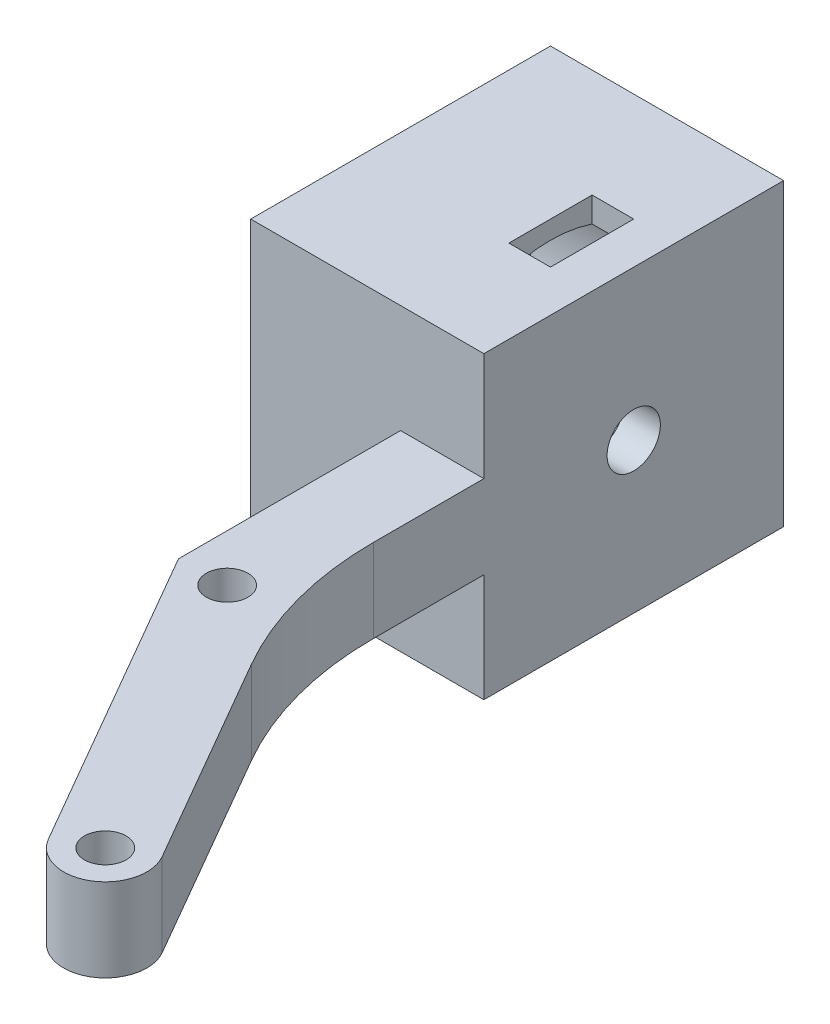
SolidWorks part; units mm, degrees
material "PLA"
ref_plane "Front Plane" through (0, 0, 0) normal (0, 0, 1) x (1, 0, 0)
ref_plane "Top Plane" through (0, 0, 0) normal (0, 1, 0) x (1, 0, 0)
ref_plane "Right Plane" through (0, 0, 0) normal (1, 0, 0) x (0, 0, -1)
sketch "Sketch1" plane through (0, 0, 0) normal (0, 1, 0) x (1, 0, 0)
  line L0 (-6.35, -14.4015) -> (-6.35, 2.54)
  line L1 (0, -12.7) -> (0, 25.4)
  line L2 (0, 25.4) -> (-17.78, 25.4)
  line L3 (-17.78, 25.4) -> (-17.78, 2.54)
  line L4 (-17.78, 2.54) -> (-6.35, 2.54)
  line L5 (0, -12.7) -> (12.7, -34.697)
  line L6 (-6.35, -14.4015) -> (7.2007, -37.872)
  line L7 (0, -12.7) -> (-5.4993, -15.875) construction
  arc A0 (7.2007, -37.872) -> (12.7, -34.697) centre (9.9504, -36.2845) ccw
  circle A1 centre (9.9504, -36.2845) radius 1.5875
  circle A2 centre (-2.7496, -14.2875) radius 1.5875
  dimension "D1" = 3.175
  dimension "D2" = 3.175
  dimension "D6" = 3.175
  dimension "D3" = 150
  dimension "D4" = 6.35
  dimension "D8" = 25.4
  dimension "D10" = 17.78
  dimension "D11" = 38.1
  dimension "D12" = 22.86
  dimension "D13" = 12.7
extrude "Boss-Extrude1" add sketch "Sketch1" along normal blind 22.86
sketch "Sketch2" plane through (0, 22.86, 0) normal (0, 1, 0) x (1, 0, 0)
  line L1 (-6.35, -14.4015) -> (8.7882, -40.6217)
  line L2 (0, -12.7) -> (14.2875, -37.4467)
  line L3 (14.2875, -37.4467) -> (8.7882, -40.6217)
  line L4 (-6.35, -14.4015) -> (7.2007, -37.872) construction
  line L5 (12.7, -34.697) -> (0, -12.7) construction
  line L6 (-6.35, 2.54) -> (0, 2.54)
  line L7 (0, -12.7) -> (0, 25.4) construction
  line L8 (0, 2.54) -> (0, -12.7)
  line L9 (-6.35, -14.4015) -> (-6.35, 2.54)
  arc A0 (7.2007, -37.872) -> (12.7, -34.697) centre (9.9504, -36.2845) ccw construction
extrude "Top Cut" cut sketch "Sketch2" against normal blind 8.255
sketch "Sketch4" plane through (0, 0, 0) normal (0, -1, 0) x (1, 0, 0)
  line L0 (-6.35, -2.54) -> (-6.35, 14.4015)
  line L1 (-6.35, 14.4015) -> (7.2007, 37.872) construction
  line L2 (-6.35, -2.54) -> (-6.35, 14.4015) construction
  line L3 (-6.35, 14.4015) -> (8.7882, 40.6217)
  line L4 (8.7882, 40.6217) -> (14.2875, 37.4467)
  line L5 (-6.35, -2.54) -> (0, -2.54)
  line L7 (0, -2.54) -> (0, 12.7)
  line L8 (0, 12.7) -> (14.2875, 37.4467)
  line L9 (12.7, 34.697) -> (0, 12.7) construction
  arc A0 (12.7, 34.697) -> (7.2007, 37.872) centre (9.9504, 36.2845) ccw construction
extrude "Bottom Cut" cut sketch "Sketch4" against normal blind 8.255
sketch "Sketch3" plane through (0, 22.86, 0) normal (0, 1, 0) x (1, 0, 0)
  line L0 (-17.78, 25.4) -> (-19.05, 24.13)
  line L1 (-19.05, 24.13) -> (-17.78, 22.86)
  line L2 (-17.78, 25.4) -> (-17.78, 2.54) construction
  line L12 (-17.78, 25.4) -> (0, 25.4)
  line L13 (0, 25.4) -> (0, 0)
  line L14 (0, 2.54) -> (0, 25.4) construction
  line L16 (-19.05, 21.59) -> (-17.78, 20.32)
  line L17 (-17.78, 22.86) -> (-19.05, 21.59)
  line L18 (-19.05, 19.05) -> (-17.78, 17.78)
  line L19 (-17.78, 20.32) -> (-19.05, 19.05)
  line L20 (-19.05, 16.51) -> (-17.78, 15.24)
  line L21 (-17.78, 17.78) -> (-19.05, 16.51)
  line L22 (-19.05, 13.97) -> (-17.78, 12.7)
  line L23 (-17.78, 15.24) -> (-19.05, 13.97)
  line L24 (-19.05, 11.43) -> (-17.78, 10.16)
  line L25 (-17.78, 12.7) -> (-19.05, 11.43)
  line L26 (-19.05, 8.89) -> (-17.78, 7.62)
  line L27 (-17.78, 10.16) -> (-19.05, 8.89)
  line L28 (-19.05, 6.35) -> (-17.78, 5.08)
  line L29 (-17.78, 7.62) -> (-19.05, 6.35)
  line L30 (-19.05, 3.81) -> (-17.78, 2.54)
  line L31 (-17.78, 5.08) -> (-19.05, 3.81)
  line L32 (-19.05, 1.27) -> (-17.78, 0)
  line L33 (-17.78, 2.54) -> (-19.05, 1.27)
  line L34 (-17.78, 0) -> (0, 0)
  dimension "D1" = 2.54
  dimension "D2" = 135
  dimension "D3" = 10
extrude "Boss-Extrude2" [suppressed] add sketch "Sketch3" against normal up to surface (5.08 mm away) contours L13 L34 L32 L33 L30 L31 L28 L29 L26 L27 L24 L25 L22 L23 L20 L21 L18 L19 L16 L17 L1 L0 L12 up to face at (-8.89, 0, -13.97)
sketch "Sketch5" plane through (-17.78, 0, 0) normal (-1, 0, 0) x (0, 0, 1)
  line L1 (-25.4, 0) -> (-2.54, 0)
  line L2 (-25.4, 0) -> (-25.4, 22.86)
  line L3 (-25.4, 22.86) -> (-2.54, 22.86)
  line L4 (-2.54, 0) -> (-2.54, 22.86)
  line L5 (-25.4, 0) -> (-2.54, 22.86) construction
  line L6 (-25.4, 22.86) -> (-2.54, 0) construction
  circle A0 centre (-13.97, 11.43) radius 10.033
  point P0 (-13.97, 11.43)
  dimension "D1" = 20.066
extrude "Cut-Extrude1" cut sketch "Sketch5" against normal blind 14.986 contours A0 region at (-17.78, 11.43, -13.97)
sketch "Sketch7" plane through (0, 0, 0) normal (1, 0, 0) x (0, 0, -1)
  line L0 (2.54, 22.86) -> (25.4, 22.86) construction
  line L1 (2.54, 0) -> (25.4, 0)
  line L2 (2.54, 0) -> (2.54, 22.86)
  line L3 (2.54, 22.86) -> (25.4, 22.86)
  line L4 (25.4, 0) -> (25.4, 22.86)
  line L5 (2.54, 0) -> (25.4, 22.86) construction
  line L6 (2.54, 22.86) -> (25.4, 0) construction
  line L7 (25.4, 22.86) -> (25.4, 0) construction
  line L9 (2.54, 0) -> (25.4, 0) construction
  circle A0 centre (13.97, 11.43) radius 2.032
  point P0 (13.97, 11.43)
  dimension "D1" = 4.064
extrude "Cut-Extrude2" cut sketch "Sketch7" against normal through all contours A0 region at (0, 11.43, -13.97)
sketch "Sketch8" plane through (0, 22.86, 0) normal (0, 1, 0) x (1, 0, 0)
  line L0 (0, 2.54) -> (0, 25.4) construction
  line L1 (-6.35, 10.795) -> (-3.175, 10.795)
  line L2 (-6.35, 10.795) -> (-6.35, 17.145)
  line L3 (-6.35, 17.145) -> (-3.175, 17.145)
  line L4 (-3.175, 10.795) -> (-3.175, 17.145)
  line L5 (-6.35, 10.795) -> (-3.175, 17.145) construction
  line L6 (-6.35, 17.145) -> (-3.175, 10.795) construction
  line L7 (-17.78, 25.4) -> (-17.78, 2.54) construction
  line L11 (-17.78, 24.003) -> (-17.78, 3.937) construction
  point P0 (-4.7625, 13.97)
  point P12 (-17.78, 13.97)
  dimension "D1" = 3.175
  dimension "D2" = 6.35
  dimension "D3" = 3.175
extrude "Cut-Extrude3" cut sketch "Sketch8" against normal up to surface (1.9126 mm away) up to face at (-2.794, 11.43, -3.937)
sketch "Sketch9" [suppressed] plane through (0, 0, 0) normal (0, -1, 0) x (1, 0, 0)
  line L0 (0, -2.54) -> (0, -25.4) construction
  line L1 (-6.35, -17.145) -> (-3.175, -17.145)
  line L2 (-6.35, -17.145) -> (-6.35, -10.795)
  line L3 (-6.35, -10.795) -> (-3.175, -10.795)
  line L4 (-3.175, -17.145) -> (-3.175, -10.795)
  line L5 (-6.35, -17.145) -> (-3.175, -10.795) construction
  line L6 (-6.35, -10.795) -> (-3.175, -17.145) construction
  line L7 (-17.78, -2.54) -> (-17.78, -25.4) construction
  point P0 (-4.7625, -13.97)
  point P11 (-17.78, -13.97)
  dimension "D1" = 3.175
  dimension "D2" = 6.35
  dimension "D3" = 3.175
extrude "Cut-Extrude4" [suppressed] cut sketch "Sketch9" against normal up to next
fillet "Fillet1" radius 25.4 1 edges at (0, 11.43, 12.7)
